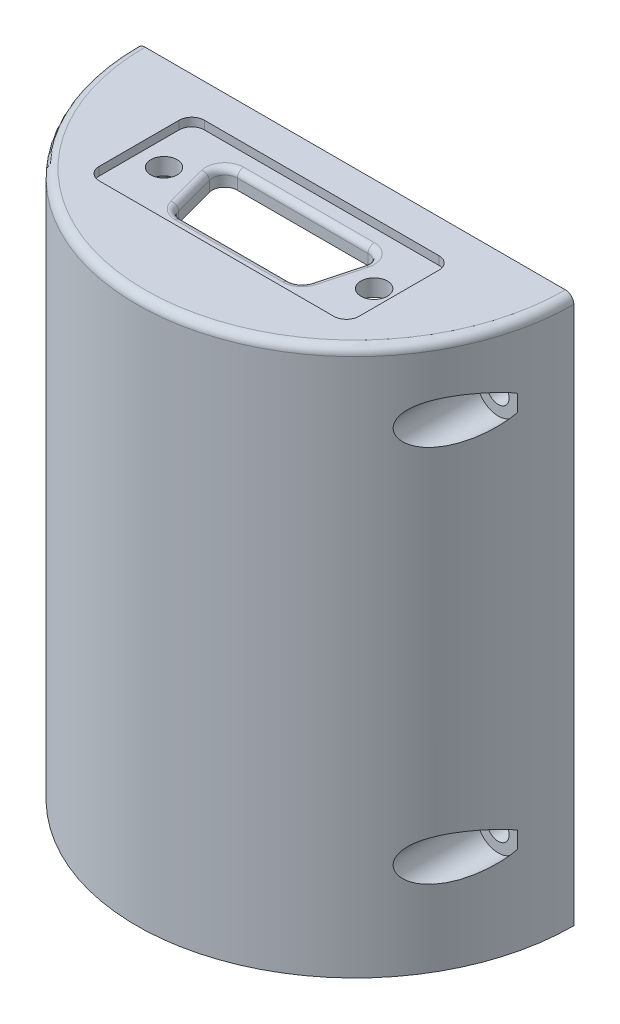
SolidWorks part; units mm, degrees
material "ABS"
ref_plane "Спереди" through (0, 0, 0) normal (0, 0, 1) x (1, 0, 0)
ref_plane "Сверху" through (0, 0, 0) normal (0, 1, 0) x (1, 0, 0)
ref_plane "Справа" through (0, 0, 0) normal (1, 0, 0) x (0, 0, -1)
sketch "Эскиз1" plane through (0, 0, 0) normal (0, 1, 0) x (1, 0, 0)
  line L0 (-26, 0) -> (-23, 0)
  line L1 (23, 0) -> (26, 0)
  arc A2 (26, 0) -> (-26, 0) centre (0, 0) cw
  arc A3 (23, 0) -> (-23, 0) centre (0, 0) cw
  dimension "D1" = 23
  dimension "D2" = 26
extrude "Бобышка-Вытянуть1" add sketch "Эскиз1" along normal blind 65
sketch "Эскиз2" plane through (0, 65, 0) normal (0, 1, 0) x (1, 0, 0)
  line L0 (-26, 0) -> (26, 0)
  arc A3 (26, 0) -> (-26, 0) centre (0, 0) cw
  arc A4 (-26, 0) -> (26, 0) centre (0, 0) ccw construction
sketch "Эскиз12" plane through (0, 0, 0) normal (0, 0, -1) x (-1, 0, 0)
  line L0 (23, 65) -> (23, 0) construction
  line L2 (23, 11.5) -> (23, 56.5) construction
  line L4 (23, 11.5) -> (23, 56.5) construction
  line L5 (23, 65) -> (23, 0) construction
  line L6 (0, 59.3805) -> (0, 0) construction
  line L7 (-23, 0) -> (23, 0) construction
  line L8 (23, 65) -> (23, 0) construction
  circle A1 centre (23, 56.5) radius 3
  circle A3 centre (23, 11.5) radius 3
  circle A4 centre (-23, 56.5) radius 3
  circle A5 centre (-23, 11.5) radius 3
  point P8 (23, 34)
  dimension "D3" = 6
  dimension "D1" = 45
  dimension "D2" = 34
extrude "Бобышка-Вытянуть5" add sketch "Эскиз12" against normal up to surface (12.6095 mm away) up to face at (0, 32.5, 11.5)
sketch "Эскиз16" plane through (0, 0, 0) normal (0, 0, -1) x (-1, 0, 0)
  line L0 (0, 60.4355) -> (0, 0) construction
  circle A1 centre (23, 56.5) radius 1.3
  circle A3 centre (23, 11.5) radius 1.3
  circle A4 centre (-23, 11.5) radius 1.3
  circle A5 centre (-23, 56.5) radius 1.3
  circle A6 centre (-23, 56.5) radius 2.5
  circle A7 centre (-23, 11.5) radius 2.5
  circle A8 centre (23, 11.5) radius 2.5
  circle A9 centre (23, 56.5) radius 2.5
  dimension "D1" = 2.6
  dimension "D2" = 5
extrude "Вырез-Вытянуть2" cut sketch "Эскиз16" against normal through all contours A1 | A3 | A4 | A5
extrude "Бобышка-Вытянуть6" add sketch "Эскиз2" against normal blind 3
fillet "Скругление1" radius 1 1 edges at (0, 65, 26)
extrude "Вырез-Вытянуть4" cut sketch "Эскиз16<4>" against normal through all from offset 6 contours A9 | A7 | A6 | A8 offset against normal yes
sketch "Эскиз16<4>" plane through (0, 0, 0) normal (0, 0, -1) x (-1, 0, 0) same geometry as "Эскиз16"
ref_plane "Плоскость1" through (-22.5167, 0, 13) normal (-0.866, 0, 0.5) x (0, -1, 0)
sketch "Эскиз24" plane through (0, 65, 0) normal (0, 1, 0) x (1, 0, 0)
  line L1 (-15.45, -4) -> (15.45, -4)
  line L2 (-15.45, -4) -> (-15.45, -16.5)
  line L3 (-15.45, -16.5) -> (15.45, -16.5)
  line L4 (15.45, -4) -> (15.45, -16.5)
  point P4 (0, -4)
  point P6 (0, -16.5)
  dimension "D1" = 12.5
  dimension "D2" = 30.9
  dimension "D3" = 4
extrude "Вырез-Вытянуть8" cut sketch "Эскиз24" against normal blind 1
sketch "Эскиз25" plane through (0, 64, 0) normal (0, 1, 0) x (1, 0, 0)
  line L0 (-9.7236, -6.25) -> (-7.58, -14.25)
  line L1 (-7.58, -14.25) -> (7.58, -14.25)
  line L2 (-9.7236, -6.25) -> (9.7236, -6.25)
  line L3 (9.7236, -6.25) -> (7.58, -14.25)
  line L4 (-15.45, -4) -> (-15.45, -16.5) construction
  point P2 (8.6518, -10.25)
  point P5 (-8.6518, -10.25)
  point P8 (-15.45, -10.25)
  point P9 (0, -6.25)
  point P11 (0, -14.25)
  dimension "D1" = 15.16
  dimension "D2" = 8
  dimension "D3" = 30
extrude "Вырез-Вытянуть9" cut sketch "Эскиз25" against normal up to next
fillet "Скругление2" radius 1.5 8 edges at (-15.45, 64.5, 16.5) (-7.58, 63, 14.25) (-9.7236, 63, 6.25) (-15.45, 64.5, 4) (9.7236, 63, 6.25) (7.58, 63, 14.25) (15.45, 64.5, 16.5) (15.45, 64.5, 4)
fillet "Скругление3" radius 0.75 8 edges at (-8.9588, 64, 6.8369) (0, 64, 6.25) (8.9588, 64, 6.8369) (8.5478, 64, 10.6382) (7.3422, 64, 13.94) (0, 64, 14.25) (-7.3422, 64, 13.94) (-8.5478, 64, 10.6382)
hole_wizard "Сверло под метчик  спиральное M31" positions "Эскиз26" profile "Эскиз27" hole size "M3x0.5" standard "Ansi Metric"
sketch "Эскиз26" plane through (0, 64, 0) normal (0, 1, 0) x (1, 0, 0)
  line L0 (-15.45, -5.5) -> (-15.45, -15) construction
  point P0 (-12.5, -10.25)
  point P2 (12.5, -10.25)
  point P9 (0, 0)
  point P12 (-15.45, -10.25)
  dimension "D1" = 25
  dimension "D2" = 12.5
sketch "Эскиз27" plane through (-12.5, 64, 10.25) normal (1, 0, 0) x (0, 0, 1)
  line L0 (0, 0) -> (0, 10.9464)
  line L1 (0, 10.9464) -> (1.575, 10)
  line L2 (1.575, 10) -> (1.575, 0)
  line L5 (1.575, 0) -> (0, 0)
  line L10 (0, 10.9464) -> (-1.575, 10) construction
  line L11 (0, -6.35) -> (0, 107.95) construction
  dimension "Диаметр отверстия" = 3.15
  dimension "Глубина отверстия" = 10
  dimension "Угол заточки сверла" = 118
